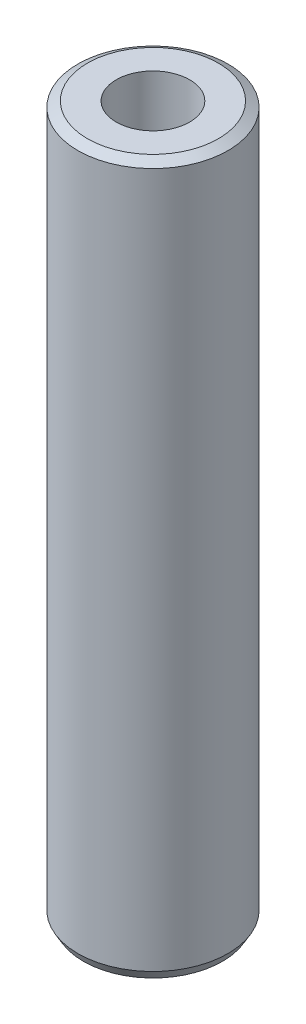
SolidWorks part; units mm, degrees
ref_plane "Front Plane" through (0, 0, 0) normal (0, 0, 1) x (1, 0, 0)
ref_plane "Top Plane" through (0, 0, 0) normal (0, 1, 0) x (1, 0, 0)
ref_plane "Right Plane" through (0, 0, 0) normal (1, 0, 0) x (0, 0, -1)
sketch "Sketch1" plane through (0, 0, 0) normal (0, 1, 0) x (1, 0, 0)
  circle A0 centre (0, 0) radius 47.5
  dimension "SHAFT_OD" = 95
extrude "Boss-Extrude1" add sketch "Sketch1" along normal blind 449.5039
sketch "Sketch2" plane through (0, 0, 0) normal (0, 1, 0) x (1, 0, 0)
  circle A0 centre (0, 0) radius 23.2237
  dimension "BORE_D" = 46.4474
extrude "Cut-Extrude1" cut sketch "Sketch2" along normal through all
chamfer "Chamfer1" distance 3.4954 angle 60 2 edges at (0, 449.5039, 47.5) (0, 0, 47.5) first distance on face at (0, 449.5039, 47.5) first distance on face at (0, 0, 23.2237)
